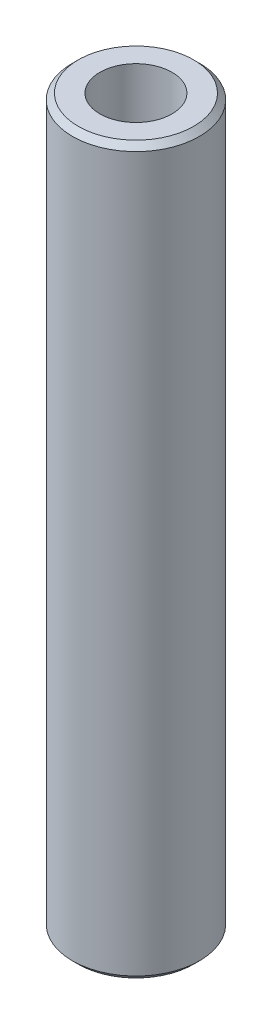
SolidWorks part; units mm, degrees
ref_plane "Front Plane" through (0, 0, 0) normal (0, 0, 1) x (1, 0, 0)
ref_plane "Top Plane" through (0, 0, 0) normal (0, 1, 0) x (1, 0, 0)
ref_plane "Right Plane" through (0, 0, 0) normal (1, 0, 0) x (0, 0, -1)
sketch "Sketch1" plane through (0, 0, 0) normal (0, 1, 0) x (1, 0, 0)
  circle A0 centre (0, 0) radius 52.5
  dimension "SHAFT_OD" = 105
extrude "Boss-Extrude1" add sketch "Sketch1" along normal blind 600
sketch "Sketch2" plane through (0, 0, 0) normal (0, 1, 0) x (1, 0, 0)
  circle A0 centre (0, 0) radius 29.8314
  dimension "BORE_D" = 59.6629
extrude "Cut-Extrude1" cut sketch "Sketch2" along normal through all
chamfer "Chamfer1" distance 4.805 angle 45 2 edges at (0, 600, 52.5) (0, 0, 52.5)
